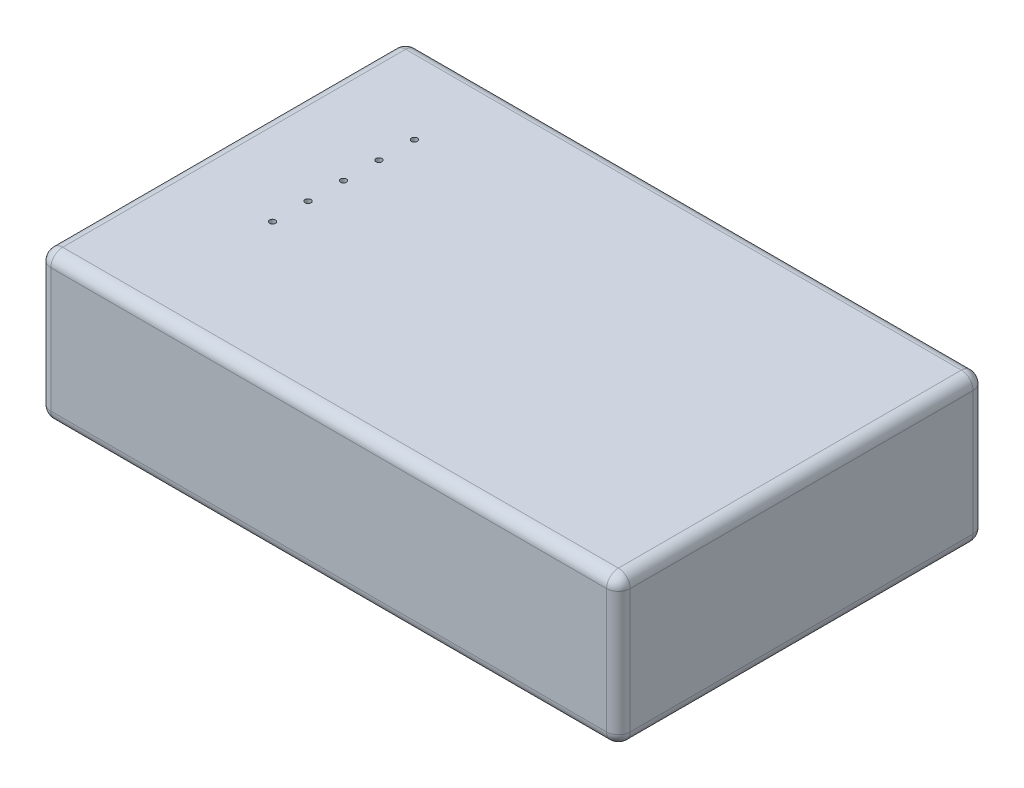
SolidWorks part; units mm, degrees
ref_plane "Front Plane" through (0, 0, 0) normal (0, 0, 1) x (1, 0, 0)
ref_plane "Top Plane" through (0, 0, 0) normal (0, 1, 0) x (1, 0, 0)
ref_plane "Right Plane" through (0, 0, 0) normal (1, 0, 0) x (0, 0, -1)
sketch "Sketch2" plane through (0, 0, 0) normal (0, 1, 0) x (1, 0, 0)
  line L1 (-49, -31) -> (49, -31)
  line L2 (-49, -31) -> (-49, 31)
  line L3 (-49, 31) -> (49, 31)
  line L4 (49, -31) -> (49, 31)
  line L5 (-49, -31) -> (49, 31) construction
  line L6 (-49, 31) -> (49, -31) construction
  point P0 (0, 0)
  dimension "D1" = 98
  dimension "D2" = 62
extrude "Boss-Extrude1" add sketch "Sketch2" along normal blind 25 contours L2 L1 L4 L3
sketch "Sketch3" plane through (-49, 0, 0) normal (-1, 0, 0) x (0, 0, 1)
  line L0 (31, 25) -> (-31, 25) construction
  line L1 (-13.907, 21) -> (-23.407, 21)
  line L2 (-13.907, 21) -> (-13.907, 9)
  line L3 (-13.907, 9) -> (-23.407, 9)
  line L4 (-23.407, 21) -> (-23.407, 9)
  line L5 (-13.907, 21) -> (-23.407, 9) construction
  line L6 (-13.907, 9) -> (-23.407, 21) construction
  point P0 (-18.657, 15)
  dimension "D1" = 4
  dimension "D2" = 12
  dimension "D3" = 9.5
extrude "Boss-Extrude4" add sketch "Sketch3" against normal blind 1 contours L2 L1 L4 L3
extrude "Cut-Extrude1" cut sketch "Sketch3<5>" against normal blind 1
sketch "Sketch3<5>" plane through (-49, 0, 0) normal (-1, 0, 0) x (0, 0, 1) same geometry as "Sketch3"
sketch "Sketch4" plane through (-48, 0, 0) normal (-1, 0, 0) x (0, 0, 1)
  line L0 (-13.907, 21) -> (-23.407, 21) construction
  line L1 (-23.407, 21) -> (-23.407, 9) construction
  circle A0 centre (-18.407, 16) radius 3.25
  dimension "D1" = 6.5
  dimension "D2" = 5
  dimension "D3" = 5
extrude "Cut-Extrude2" cut sketch "Sketch4" against normal blind 10
sketch "Sketch5" plane through (-38, 0, 0) normal (-1, 0, 0) x (0, 0, 1)
  circle A0 centre (-18.407, 16) radius 0.5
  dimension "D1" = 1
extrude "Boss-Extrude5" add sketch "Sketch5" along normal blind 8
sketch "Sketch6" plane through (-49, 0, 0) normal (-1, 0, 0) x (0, 0, 1)
  line L0 (-13.907, 9) -> (-13.907, 21) construction
  line L1 (-9.907, 21) -> (-2.907, 21)
  line L2 (-9.907, 21) -> (-9.907, 7)
  line L3 (-9.907, 7) -> (-2.907, 7)
  line L4 (-2.907, 21) -> (-2.907, 7)
  line L5 (-9.907, 21) -> (-2.907, 7) construction
  line L6 (-9.907, 7) -> (-2.907, 21) construction
  line L11 (31, 25) -> (-31, 25) construction
  point P0 (-6.407, 14)
  dimension "D1" = 4
  dimension "D2" = 7
  dimension "D3" = 14
  dimension "D4" = 4
extrude "Cut-Extrude9" cut sketch "Sketch6" against normal blind 10
sketch "Sketch7" plane through (-39, 0, 0) normal (-1, 0, 0) x (0, 0, 1)
  line L0 (-2.907, 21) -> (-9.907, 21) construction
  line L1 (-5.4664, 19) -> (-3.907, 19)
  line L2 (-5.4664, 19) -> (-5.4664, 9)
  line L3 (-5.4664, 9) -> (-3.907, 9)
  line L4 (-3.907, 19) -> (-3.907, 9)
  line L5 (-9.907, 7) -> (-2.907, 7) construction
  line L6 (-2.907, 7) -> (-2.907, 21) construction
  dimension "D1" = 2
  dimension "D2" = 2
  dimension "D3" = 1
extrude "Boss-Extrude6" add sketch "Sketch7" along normal blind 9
sketch "Sketch8" plane through (-49, 0, 0) normal (-1, 0, 0) x (0, 0, 1)
  line L0 (31, 25) -> (-31, 25) construction
  line L1 (19.593, 20) -> (4.593, 20)
  line L2 (19.593, 20) -> (19.593, 10)
  line L3 (19.593, 10) -> (4.593, 10)
  line L4 (4.593, 20) -> (4.593, 10)
  line L5 (-2.907, 7) -> (-2.907, 21) construction
  dimension "D1" = 5
  dimension "D2" = 10
  dimension "D3" = 15
  dimension "D4" = 7.5
extrude "Boss-Extrude7" add sketch "Sketch8" along normal blind 2 draft 30
ref_plane "Plane2" [suppressed] through (0, 12, 0) normal (0, -1, 0) x (-1, 0, 0)
sketch "Sketch9" [suppressed] plane through (0, 12, 0) normal (0, -1, 0) x (-1, 0, 0)
  line L0 (51, -5.7477) -> (51, -18.4383) construction
  line L1 (51, -7.6447) -> (51, -16.8055)
  spline S0 degree 2 poles (51, -7.6447) (51.419, -11.6679) (53.8134, -15.0002) knots 0 0 0 1 1 1
  spline S1 degree 2 poles (53.8134, -15.0002) (53.1044, -16.8217) (51, -16.8055) knots 0 0 0 1 1 1
extrude "Boss-Extrude8" [suppressed] add sketch "Sketch9" against normal blind 6
fillet "Fillet5" radius 2 12 edges at (49, 12.5, -31) (0, 25, -31) (-49, 12.5, -31) (0, 0, -31) (-49, 0, 0) (-49, 12.5, 31) (0, 0, 31) (49, 0, 0) (49, 25, 0) (49, 12.5, 31) (-49, 25, 0) (0, 25, 31)
sketch "Sketch10" plane through (0, 0, 0) normal (0, -1, 0) x (1, 0, 0)
  line L0 (-47, -29) -> (47, -29) construction
  line L1 (47, 29) -> (-47, 29) construction
  line L2 (47, -29) -> (47, 29) construction
  line L3 (-47, 29) -> (-47, -29) construction
  circle A0 centre (-43, -25.5) radius 2.5
  circle A1 centre (-43, 25.5) radius 2.5
  circle A2 centre (43, 25.5) radius 2.5
  circle A3 centre (43, -25.5) radius 2.5
  dimension "D1" = 5
  dimension "D2" = 5
  dimension "D3" = 5
  dimension "D4" = 5
  dimension "D5" = 3.5
  dimension "D6" = 3.5
  dimension "D7" = 3.5
  dimension "D8" = 3.5
  dimension "D9" = 4
  dimension "D10" = 4
  dimension "D11" = 4
  dimension "D12" = 4
extrude "Cut-Extrude10" cut sketch "Sketch10" against normal blind 6
sketch "Sketch11" plane through (0, 25, 0) normal (0, 1, 0) x (1, 0, 0)
  line L0 (47, 29) -> (-47, 29) construction
  line L1 (-47, 29) -> (-47, -29) construction
  circle A0 centre (-33, 16.5) radius 0.5
  circle A1 centre (-33, 10.5) radius 0.5
  circle A2 centre (-33, 4.5) radius 0.5
  circle A3 centre (-33, -1.5) radius 0.5
  circle A4 centre (-33, -7.5) radius 0.5
  dimension "D1" = 1
  dimension "D2" = 1
  dimension "D3" = 1
  dimension "D4" = 1
  dimension "D5" = 1
  dimension "D6" = 12.5
  dimension "D7" = 6
  dimension "D8" = 6
  dimension "D9" = 6
  dimension "D10" = 6
  dimension "D11" = 14
extrude "Cut-Extrude11" cut sketch "Sketch11" against normal blind 3
